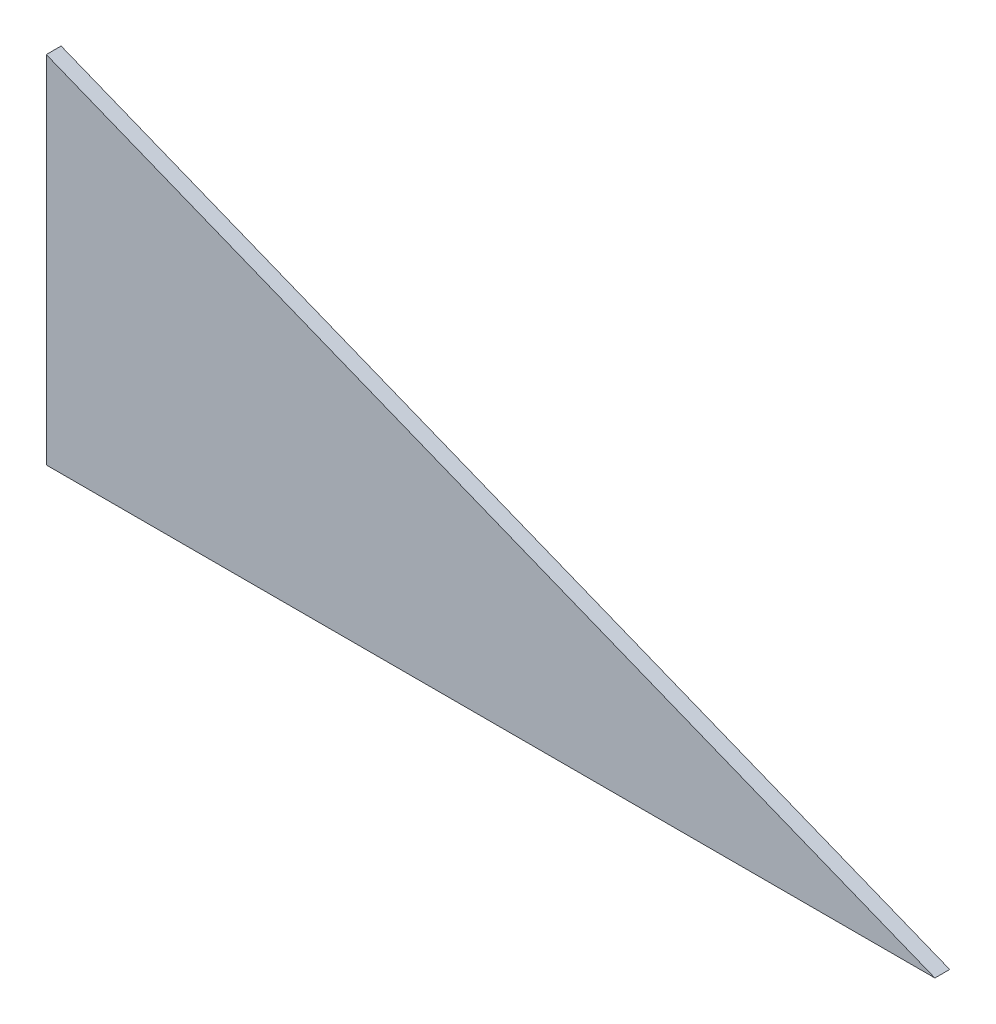
SolidWorks part; units mm, degrees
material "Plain Carbon Steel"
ref_plane "Front Plane" through (0, 0, 0) normal (0, 0, 1) x (1, 0, 0)
ref_plane "Top Plane" through (0, 0, 0) normal (0, 1, 0) x (1, 0, 0)
ref_plane "Right Plane" through (0, 0, 0) normal (1, 0, 0) x (0, 0, -1)
sketch "Sketch1" plane through (0, 0, 0) normal (0, 0, 1) x (1, 0, 0)
  line L0 (0, 76.2) -> (0, 0)
  line L1 (0, 0) -> (190.5, 0)
  line L3 (0, 76.2) -> (190.5, 0)
  dimension "D1" = 190.5
  dimension "D2" = 76.2
extrude "Boss-Extrude1" add sketch "Sketch1" along normal blind 3.175
